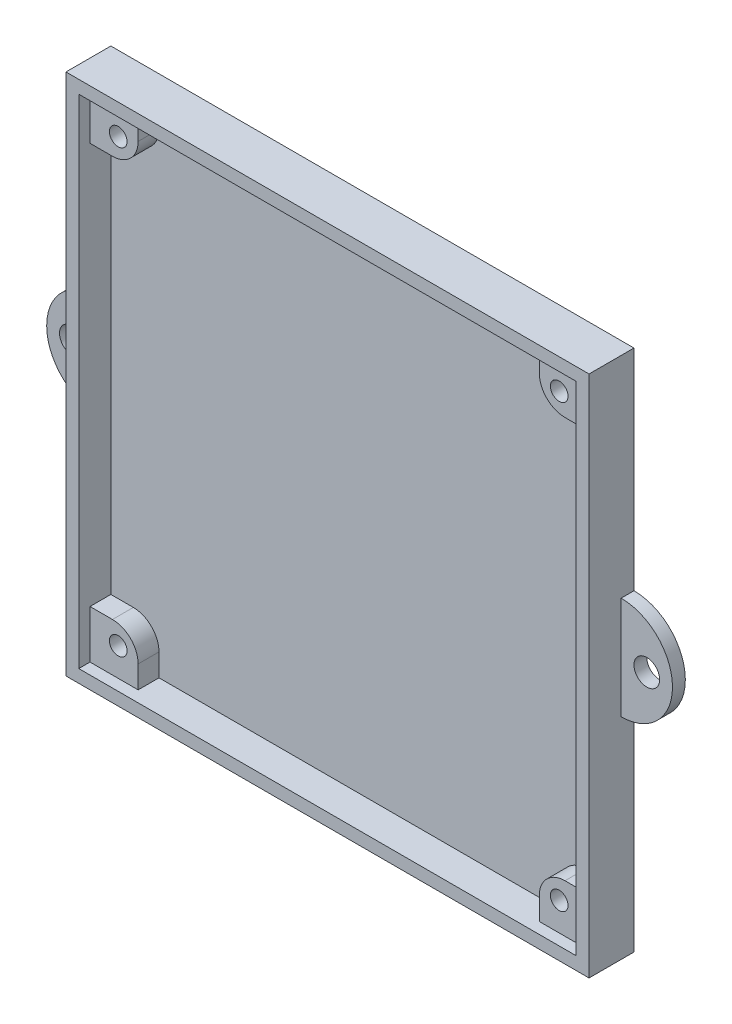
SolidWorks part; units mm, degrees
ref_plane "Front Plane" through (0, 0, 0) normal (0, 0, 1) x (1, 0, 0)
ref_plane "Top Plane" through (0, 0, 0) normal (0, 1, 0) x (1, 0, 0)
ref_plane "Right Plane" through (0, 0, 0) normal (1, 0, 0) x (0, 0, -1)
sketch "Sketch1" plane through (0, 0, 0) normal (0, 0, 1) x (1, 0, 0)
  line L1 (-38.75, 38.75) -> (38.75, 38.75) construction
  line L2 (-38.75, 38.75) -> (-38.75, -38.75) construction
  line L3 (-38.75, -38.75) -> (38.75, -38.75) construction
  line L4 (38.75, 38.75) -> (38.75, -38.75) construction
  line L5 (-38.75, 38.75) -> (38.75, -38.75) construction
  line L6 (-38.75, -38.75) -> (38.75, 38.75) construction
  line L7 (-40.75, 40.75) -> (40.75, 40.75)
  line L8 (-40.75, 40.75) -> (-40.75, -40.75)
  line L9 (-40.75, -40.75) -> (40.75, -40.75)
  line L10 (40.75, 40.75) -> (40.75, -40.75)
  line L11 (-40.75, 40.75) -> (40.75, -40.75) construction
  line L12 (-40.75, -40.75) -> (40.75, 40.75) construction
  point P0 (0, 0)
  point P6 (0, 0)
  dimension "D1" = 2
  dimension "D2" = 77.5
  dimension "D3" = 77.5
extrude "Boss-Extrude2" add sketch "Sketch1" along normal blind 7
sketch "Sketch3" plane through (0, 0, 7) normal (0, 0, 1) x (1, 0, 0)
  line L1 (-38.75, 38.75) -> (38.75, 38.75)
  line L2 (-38.75, 38.75) -> (-38.75, -38.75)
  line L3 (-38.75, -38.75) -> (38.75, -38.75)
  line L4 (38.75, 38.75) -> (38.75, -38.75)
  line L5 (-38.75, 38.75) -> (38.75, -38.75) construction
  line L6 (-38.75, -38.75) -> (38.75, 38.75) construction
  point P0 (0, 0)
extrude "Cut-Extrude2" cut sketch "Sketch3" against normal blind 5
sketch "Sketch5" plane through (0, 0, 2) normal (0, 0, 1) x (1, 0, 0)
  line L1 (-38.75, 38.75) -> (-31.25, 38.75)
  line L2 (-38.75, 38.75) -> (-38.75, 31.25)
  line L3 (-38.75, 31.25) -> (-31.25, 31.25)
  line L4 (-31.25, 38.75) -> (-31.25, 31.25)
  line L5 (38.75, 38.75) -> (31.25, 38.75)
  line L6 (38.75, 38.75) -> (38.75, 31.25)
  line L7 (38.75, 31.25) -> (31.25, 31.25)
  line L8 (31.25, 38.75) -> (31.25, 31.25)
  line L9 (38.75, -38.75) -> (31.25, -38.75)
  line L10 (38.75, -38.75) -> (38.75, -31.25)
  line L11 (38.75, -31.25) -> (31.25, -31.25)
  line L12 (31.25, -38.75) -> (31.25, -31.25)
  line L13 (-38.75, -38.75) -> (-31.25, -38.75)
  line L14 (-38.75, -38.75) -> (-38.75, -31.25)
  line L15 (-38.75, -31.25) -> (-31.25, -31.25)
  line L16 (-31.25, -38.75) -> (-31.25, -31.25)
  dimension "D1" = 7.5
extrude "Boss-Extrude3" add sketch "Sketch5" along normal blind 3.25
sketch "Sketch4" plane through (0, 0, 5.25) normal (0, 0, 1) x (1, 0, 0)
  line L0 (-34.35, 34.35) -> (34.35, 34.35) construction
  line L1 (34.35, 34.35) -> (34.35, -34.35) construction
  line L12 (34.35, -34.35) -> (-34.35, -34.35) construction
  line L13 (-34.35, -34.35) -> (-34.35, 34.35) construction
  line L14 (0, 38.75) -> (0, 34.35) construction
  line L15 (38.75, 38.75) -> (-38.75, 38.75) construction
  line L16 (34.35, 0) -> (38.75, 0) construction
  line L17 (38.75, -38.75) -> (38.75, 38.75) construction
  line L18 (0, -38.75) -> (0, -34.35) construction
  line L19 (-31.25, -38.75) -> (31.25, -38.75) construction
  line L20 (-38.75, 0) -> (-34.35, 0) construction
  line L21 (-38.75, 38.75) -> (-38.75, -38.75) construction
  circle A0 centre (-34.35, 34.35) radius 1.375
  circle A1 centre (34.35, 34.35) radius 1.375
  circle A2 centre (34.35, -34.35) radius 1.375
  circle A3 centre (-34.35, -34.35) radius 1.375
  dimension "D3" = 68.7
  dimension "D9" = 2.75
  dimension "D1" = 68.7
  dimension "D2" = 68.7
  dimension "D4" = 68.7
extrude "Cut-Extrude3" cut sketch "Sketch4" against normal blind 3.3
sketch "Sketch6" plane through (0, 0, 0) normal (0, 0, -1) x (-1, 0, 0)
  text T0 "<b>     XYZZY</b>\r\n<b>    MOTOR</b>\r\n<b>CONTROLLER</b>\r\n<b> PROTOTYPE</b>" font "Century Gothic" height in points 24
extrude "Cut-Extrude4" cut sketch "Sketch6" against normal blind 1
fillet "Fillet1" radius 4 4 edges at (31.25, -31.25, 3.625) (-31.25, -31.25, 3.625) (31.25, 31.25, 3.625) (-31.25, 31.25, 3.625)
sketch "Sketch7" plane through (0, 0, 0) normal (0, 0, -1) x (-1, 0, 0)
  line L0 (40.75, 40.75) -> (40.75, -40.75) construction
  line L1 (40.75, 0) -> (48.75, 0) construction
  line L2 (-40.75, -40.75) -> (-40.75, 40.75) construction
  line L5 (-40.75, -40.75) -> (-40.75, 40.75) construction
  line L6 (40.75, 8) -> (40.75, -8)
  line L7 (-40.75, -8) -> (-40.75, 8)
  line L10 (-48.75, 0) -> (-40.75, 0) construction
  arc A0 (40.75, 8) -> (40.75, -8) centre (40.75, 0) cw
  arc A1 (-40.75, 8) -> (-40.75, -8) centre (-40.75, 0) ccw
  circle A2 centre (44.75, 0) radius 2
  circle A3 centre (-44.75, 0) radius 2
  dimension "D3" = 4
  dimension "D1" = 8
extrude "Boss-Extrude4" add sketch "Sketch7" against normal blind 2
